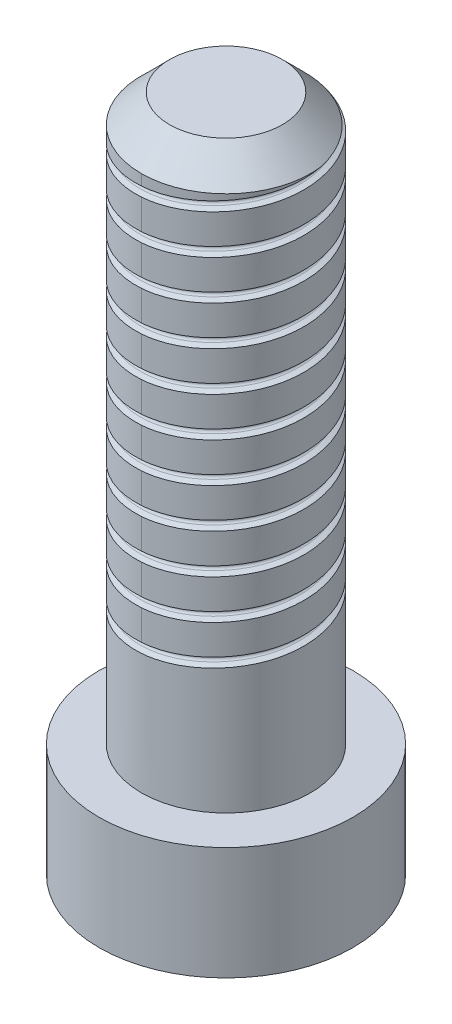
SolidWorks part; units mm, degrees
note: '?' marks a value the reader was unsure of.
ref_plane "Front Plane" through (0, 0, 0) normal (0, 0, 1) x (1, 0, 0)
ref_plane "Top Plane" through (0, 0, 0) normal (0, 1, 0) x (1, 0, 0)
ref_plane "Right Plane" through (0, 0, 0) normal (1, 0, 0) x (0, 0, -1)
sketch "Sketch1" plane through (0, 0, 0) normal (0, 1, 0) x (1, 0, 0)
  line L1 (2.5981, 0) -> (1.299, 2.25) construction
  line L2 (1.299, 2.25) -> (-1.299, 2.25) construction
  line L3 (-1.299, 2.25) -> (-2.5981, 0) construction
  line L4 (-2.5981, 0) -> (-1.299, -2.25) construction
  line L5 (-1.299, -2.25) -> (1.299, -2.25) construction
  line L6 (1.299, -2.25) -> (2.5981, 0) construction
  circle A0 centre (0, 0) radius 2.25
  dimension "D1" = 4.5
extrude "Boss-Extrude1" add sketch "Sketch1" along normal blind 12
sketch "Sketch2" plane through (0, 12, 0) normal (0, 1, 0) x (1, 0, 0)
  circle A0 centre (0, 0) radius 1.5
  dimension "D1" = 3
extrude "Cut-Extrude1" cut sketch "Sketch2" against normal blind 10 flip side to cut
ref_axis "Axis1" through (0, 2, 0) along (0, 1, 0)?
chamfer "Chamfer1" distance 0.5 angle 45 1 edges at (0, 12, 1.5)
sketch "Sketch5" plane through (0, 12, 0) normal (0, 1, 0) x (1, 0, 0)
  circle A0 centre (0, 0) radius 1.5
  dimension "D1" = 3
curve "Helix/Spiral1" pitch 0.7 height 8 turns 11.4286
ref_plane "Plane1" through (0, 12, 1.5) normal (-0.9973, -0.0741, 0) x (0, 0, 1)
sketch "Sketch7" plane through (0, 12, 1.5) normal (-0.9973, -0.0741, 0) x (0, 0, 1)
  line L0 (-0.081, -0.0303) -> (0.549, 0.2747)
  line L1 (0.549, 0.2747) -> (0.549, -0.4253)
  line L2 (0.549, -0.4253) -> (-0.081, -0.1203)
  arc A0 (-0.081, -0.0303) -> (-0.081, -0.1203) centre (-0.0592, -0.0753) ccw
  dimension "D2" = 0.05
  dimension "D1" = 0.7
sweep "Cut-Sweep1" cut profiles "Sketch7" path "Helix/Spiral1"
sketch "Sketch8" plane through (0, 0, 0) normal (0, -1, 0) x (1, 0, 0)
  line L1 (1.1547, 0) -> (0.5774, 1)
  line L2 (0.5774, 1) -> (-0.5774, 1)
  line L3 (-0.5774, 1) -> (-1.1547, 0)
  line L4 (-1.1547, 0) -> (-0.5774, -1)
  line L5 (-0.5774, -1) -> (0.5774, -1)
  line L6 (0.5774, -1) -> (1.1547, 0)
  circle A0 centre (0, 0) radius 1 construction
  dimension "D1" = 2
extrude "Cut-Extrude2" cut sketch "Sketch8" against normal blind 1.5
